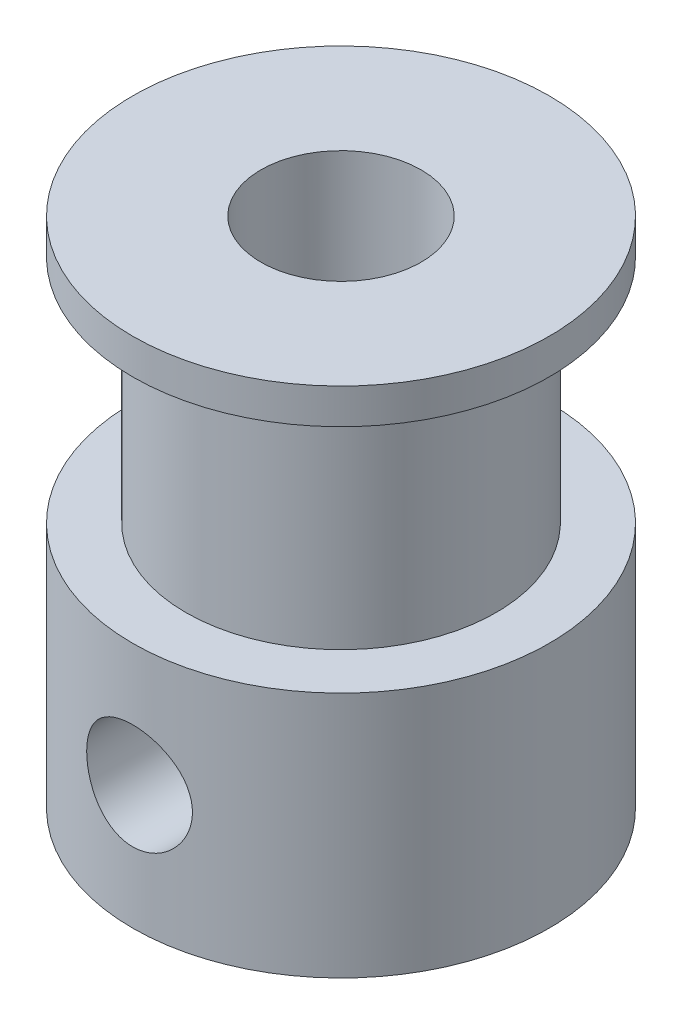
SolidWorks part; units mm, degrees
ref_plane "Plan de face" through (0, 0, 0) normal (0, 0, 1) x (1, 0, 0)
ref_plane "Plan de dessus" through (0, 0, 0) normal (0, 1, 0) x (1, 0, 0)
ref_plane "Plan de droite" through (0, 0, 0) normal (1, 0, 0) x (0, 0, -1)
sketch "Esquisse2" plane through (0, 0, 0) normal (0, 0, 1) x (1, 0, 0)
  line L1 (2.5, 16) -> (6.5, 16)
  line L2 (6.5, 16) -> (6.5, 14.9)
  line L3 (6.5, 14.9) -> (4.84, 14.9)
  line L4 (4.84, 14.9) -> (4.84, 7.7)
  line L5 (4.84, 7.7) -> (6.5, 7.7)
  line L6 (6.5, 7.7) -> (6.5, 0)
  line L7 (6.5, 0) -> (2.5, 0)
  line L8 (0, 0) -> (0, 29.6666) construction
  line L9 (2.5, 0) -> (2.5, 16)
  dimension "D1" = 5
  dimension "D2" = 13
  dimension "D3" = 16
  dimension "D4" = 7.2
  dimension "D5" = 9.68
  dimension "D6" = 1.1
revolve "Révolution1" add sketch "Esquisse2" angle 360 about L8
ref_axis "Axe1" through (0, 16, 0) along (0, -1, 0)
hole_wizard "Trou pour taraudage pour trou taraudé M41" positions "Esquisse3" profile "Esquisse4" hole size "M4" standard "ISO" end condition through all
sketch "Esquisse3" plane through (0, 0, 0) normal (0, 0, 1) x (1, 0, 0)
  line L0 (0, 7.7) -> (0, 0) construction
  line L1 (6.5, 7.7) -> (-6.5, 7.7) construction
  point P0 (0, 3.85)
sketch "Esquisse4" plane through (0, 3.85, 0) normal (1, 0, 0) x (0, 1, 0)
  line L0 (0, 0) -> (0, 6.5)
  line L1 (0, 6.5) -> (1.65, 6.5)
  line L2 (1.65, 6.5) -> (1.65, 0)
  line L5 (1.65, 0) -> (0, 0)
  line L11 (0, -6.35) -> (0, 107.95) construction
  dimension "Diamètre du perçage jusqu'au prochain" = 3.3
  dimension "Profondeur du perçage jusqu'au prochain" = 6.5
ref_plane "Plan1" through (0, 11.3, 0) normal (0, -1, 0) x (-1, 0, 0)
pattern_circular "Répétition circulaire1" count 2 every 90 about axis through (0, 16, 0) along (0, -1, 0) of "Trou pour taraudage pour trou taraudé M41"
